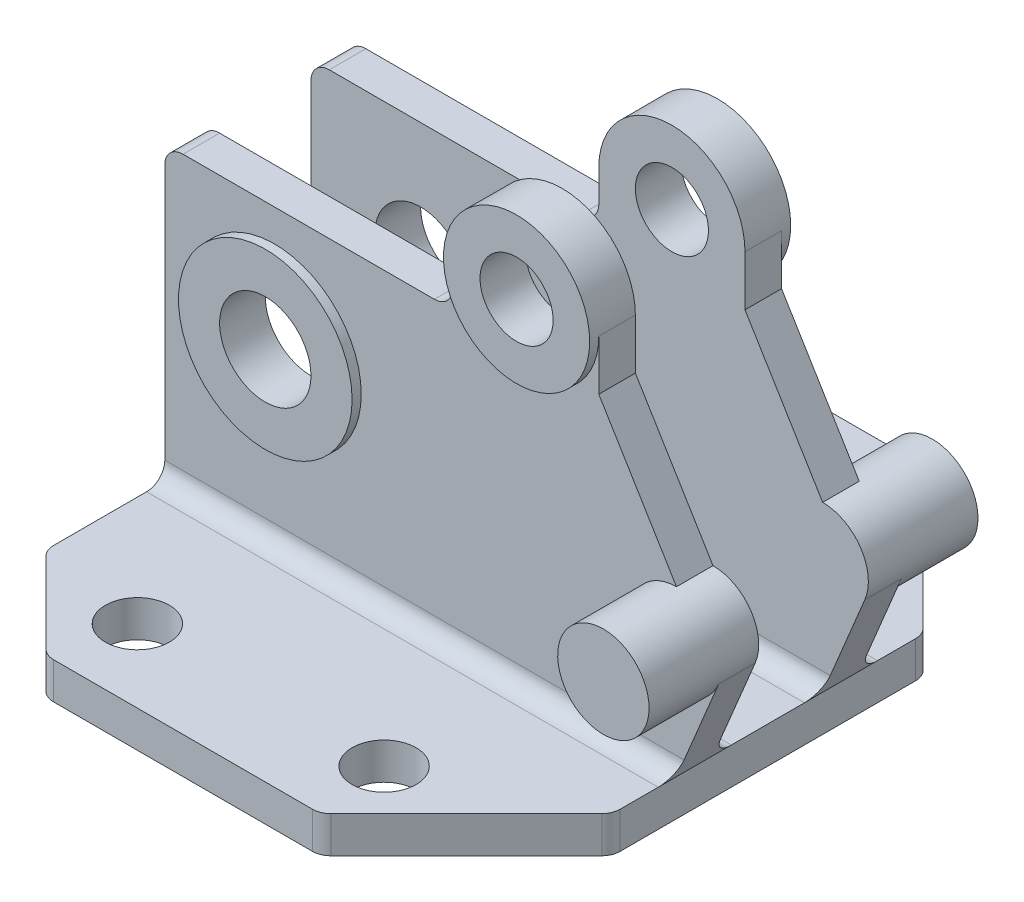
SolidWorks part; units mm, degrees
material "Cast Carbon Steel"
ref_plane "Front Plane" through (0, 0, 0) normal (0, 0, 1) x (1, 0, 0)
ref_plane "Top Plane" through (0, 0, 0) normal (0, 1, 0) x (1, 0, 0)
ref_plane "Right Plane" through (0, 0, 0) normal (1, 0, 0) x (0, 0, -1)
sketch "Sketch2" plane through (0, 0, 0) normal (0, 1, 0) x (1, 0, 0)
  line L0 (0, 10) -> (10, 0)
  line L5 (10, 0) -> (40, 0)
  line L8 (0, 10) -> (0, 56)
  line L9 (10, 66) -> (40, 66)
  line L10 (56, 16) -> (56, 50)
  line L14 (40, 0) -> (56, 16)
  line L15 (10, 0) -> (0, 0) construction
  line L16 (40, 0) -> (55.0289, 0) construction
  line L18 (28.1048, 33) -> (0, 33) construction
  line L19 (0, 56) -> (10, 66)
  line L20 (40, 66) -> (56, 50)
  circle A0 centre (12, 8) radius 3.5
  circle A1 centre (39, 8) radius 3.5
  circle A2 centre (12, 58) radius 3.5
  circle A3 centre (39, 58) radius 3.5
  dimension "D4" = 16
  dimension "D9" = 66
  dimension "D8" = 7
  dimension "D1" = 10
  dimension "D2" = 45
  dimension "D3" = 45
  dimension "D5" = 8
  dimension "D6" = 27
  dimension "D7" = 12
  dimension "D10" = 56
extrude "Boss-Extrude2" add sketch "Sketch2" along normal blind 4
fillet "Fillet1" radius 2 8 edges at (0, 2, -56) (10, 2, -66) (40, 2, -66) (56, 2, -50) (56, 2, -16) (10, 2, 0) (0, 2, -10) (40, 2, 0)
ref_plane "Plane1" through (0, 0, -33) normal (0, 0, 1) x (1, 0, 0)
sketch "Sketch3" plane through (0, 0, -33) normal (0, 0, 1) x (1, 0, 0)
  line L0 (0, 4) -> (0, 36)
  line L1 (0, 36) -> (31.5, 36)
  line L2 (47.5, 36) -> (56, 22)
  line L3 (56, 4) -> (60.6154, 15.0769)
  line L4 (10.8284, 4) -> (39.1716, 4) construction
  line L5 (31.5, 41.5) -> (31.5, 36)
  line L6 (47.5, 41.5) -> (47.5, 36)
  line L7 (40.5858, 4) -> (55.4142, 4) construction
  line L8 (56, 4) -> (0, 4)
  arc A2 (47.5, 41.5) -> (31.5, 41.5) centre (39.5, 41.5) ccw
  arc A3 (60.6154, 15.0769) -> (56, 22) centre (56, 17) ccw
  dimension "D3" = 8
  dimension "D5" = 16.5
  dimension "D6" = 10
  dimension "D1" = 32
  dimension "D2" = 37.5
  dimension "D4" = 13
  dimension "D7" = 39.5
extrude "Boss-Extrude3" add sketch "Sketch3" along normal blind 10
sketch "Sketch4" plane through (0, 0, 0) normal (-1, 0, 0) x (0, 0, 1)
  line L0 (-23, 49.5) -> (-33, 49.5) construction
  line L1 (-33, 4) -> (-27, 4)
  line L2 (-33, 4) -> (-33, 49.5)
  line L3 (-33, 49.5) -> (-27, 49.5)
  line L4 (-27, 4) -> (-27, 49.5)
  dimension "D1" = 6
extrude "Cut-Extrude2" cut sketch "Sketch4" against normal through all
fillet "Fillet2" radius 2 1 edges at (31.5, 36, -25)
sketch "Sketch7" plane through (0, 0, -23) normal (0, 0, 1) x (1, 0, 0)
  line L7 (0, 4) -> (56, 4)
  line L8 (56, 4) -> (60.6154, 15.0769)
  line L9 (56, 22) -> (47.5, 36)
  line L10 (47.5, 36) -> (47.5, 41.5)
  line L11 (31.5, 41.5) -> (31.5, 38)
  line L12 (29.5, 36) -> (0, 36)
  line L13 (0, 36) -> (0, 4)
  line L14 (0, 4) -> (56, 4)
  line L15 (56, 4) -> (60.6154, 15.0769)
  line L16 (56, 22) -> (47.5, 36)
  line L17 (47.5, 36) -> (47.5, 41.5)
  line L18 (31.5, 41.5) -> (31.5, 38)
  line L19 (29.5, 36) -> (0, 36)
  line L20 (0, 36) -> (0, 4)
  line L21 (0, 4) -> (56, 4)
  line L22 (0, 36) -> (0, 4)
  line L23 (29.5, 36) -> (0, 36)
  line L24 (31.5, 41.5) -> (31.5, 38)
  line L25 (47.5, 36) -> (47.5, 41.5)
  line L26 (56, 22) -> (47.5, 36)
  line L27 (56, 4) -> (60.6154, 15.0769)
  line L28 (0, 4) -> (56, 4) construction
  line L29 (0, 36) -> (0, 4) construction
  line L30 (29.5, 36) -> (0, 36) construction
  line L31 (31.5, 41.5) -> (31.5, 38) construction
  line L32 (47.5, 36) -> (47.5, 41.5) construction
  line L33 (56, 22) -> (47.5, 36) construction
  line L34 (56, 4) -> (60.6154, 15.0769) construction
  circle A0 centre (39.5, 41.5) radius 8
  arc A3 (60.6154, 15.0769) -> (56, 22) centre (56, 17) ccw
  arc A4 (47.5, 41.5) -> (31.5, 41.5) centre (39.5, 41.5) ccw
  arc A5 (29.5, 36) -> (31.5, 38) centre (29.5, 38) ccw
  arc A6 (60.6154, 15.0769) -> (56, 22) centre (56, 17) ccw
  arc A7 (47.5, 41.5) -> (31.5, 41.5) centre (39.5, 41.5) ccw
  arc A8 (29.5, 36) -> (31.5, 38) centre (29.5, 38) ccw
  arc A9 (29.5, 36) -> (31.5, 38) centre (29.5, 38) ccw
  arc A10 (47.5, 41.5) -> (31.5, 41.5) centre (39.5, 41.5) ccw
  arc A11 (60.6154, 15.0769) -> (56, 22) centre (56, 17) ccw
  arc A12 (29.5, 36) -> (31.5, 38) centre (29.5, 38) ccw construction
  arc A13 (47.5, 41.5) -> (31.5, 41.5) centre (39.5, 41.5) ccw construction
  arc A14 (60.6154, 15.0769) -> (56, 22) centre (56, 17) ccw construction
  circle A15 centre (12, 23) radius 9.5
  arc M26 (47.5, 41.5) -> (31.5, 41.5) centre (39.5, 41.5) ccw
  dimension "D6" = 19
  dimension "D4" = 19
  dimension "D5" = 12
  dimension "D1" = 0
  dimension "D2" = 0
extrude "Boss-Extrude5" add sketch "Sketch7" along normal blind 1 contours A0 M26 | A15 region at (39.5, 41.5, -23) region at (12, 23, -23)
sketch "Sketch9" plane through (0, 0, -22) normal (0, 0, 1) x (1, 0, 0)
  circle A0 centre (39.5, 41.5) radius 8 construction
  circle A1 centre (12, 23) radius 9.5 construction
  circle A2 centre (39.5, 41.5) radius 8
  circle A3 centre (12, 23) radius 9.5
  circle A4 centre (12, 23) radius 5
  circle A5 centre (39.5, 41.5) radius 4
  dimension "D1" = 8
  dimension "D2" = 10
extrude "Cut-Extrude4" cut sketch "Sketch9" against normal through all contours A4 | A5
sketch "Sketch10" plane through (0, 0, -23) normal (0, 0, 1) x (1, 0, 0)
  line L7 (47.5, 36) -> (47.5, 41.5)
  line L8 (31.5, 41.5) -> (31.5, 38)
  line L9 (29.5, 36) -> (0, 36)
  line L10 (0, 36) -> (0, 4)
  line L11 (0, 4) -> (56, 4)
  line L12 (56, 4) -> (60.6154, 15.0769)
  line L13 (56, 22) -> (47.5, 36)
  line L14 (47.5, 36) -> (47.5, 41.5) construction
  line L15 (31.5, 41.5) -> (31.5, 38) construction
  line L16 (29.5, 36) -> (0, 36) construction
  line L17 (0, 36) -> (0, 4) construction
  line L18 (0, 4) -> (56, 4) construction
  line L19 (56, 4) -> (60.6154, 15.0769) construction
  line L20 (56, 22) -> (47.5, 36) construction
  circle A0 centre (56, 17) radius 5
  arc A3 (31.5, 41.5) -> (47.5, 41.5) centre (39.5, 41.5) ccw
  arc A4 (29.5, 36) -> (31.5, 38) centre (29.5, 38) ccw
  arc A5 (60.6154, 15.0769) -> (56, 22) centre (56, 17) ccw
  arc A6 (31.5, 41.5) -> (47.5, 41.5) centre (39.5, 41.5) ccw construction
  arc A7 (29.5, 36) -> (31.5, 38) centre (29.5, 38) ccw construction
  arc A8 (60.6154, 15.0769) -> (56, 22) centre (56, 17) ccw construction
  dimension "D1" = 0
extrude "Boss-Extrude6" add sketch "Sketch10" along normal blind 8 contours A0
fillet "Fillet4" radius 2 1 edges at (28, 4, -23)
fillet "Fillet5" radius 2 1 edges at (28, 4, -27)
fillet "Fillet6" radius 2 1 edges at (0, 36, -25)
mirror "Mirror1" about plane through (0, 0, -33) normal (0, 0, 1) of bodies 110
equation "\"A\"= 66"
equation "\"B\"= 56"
